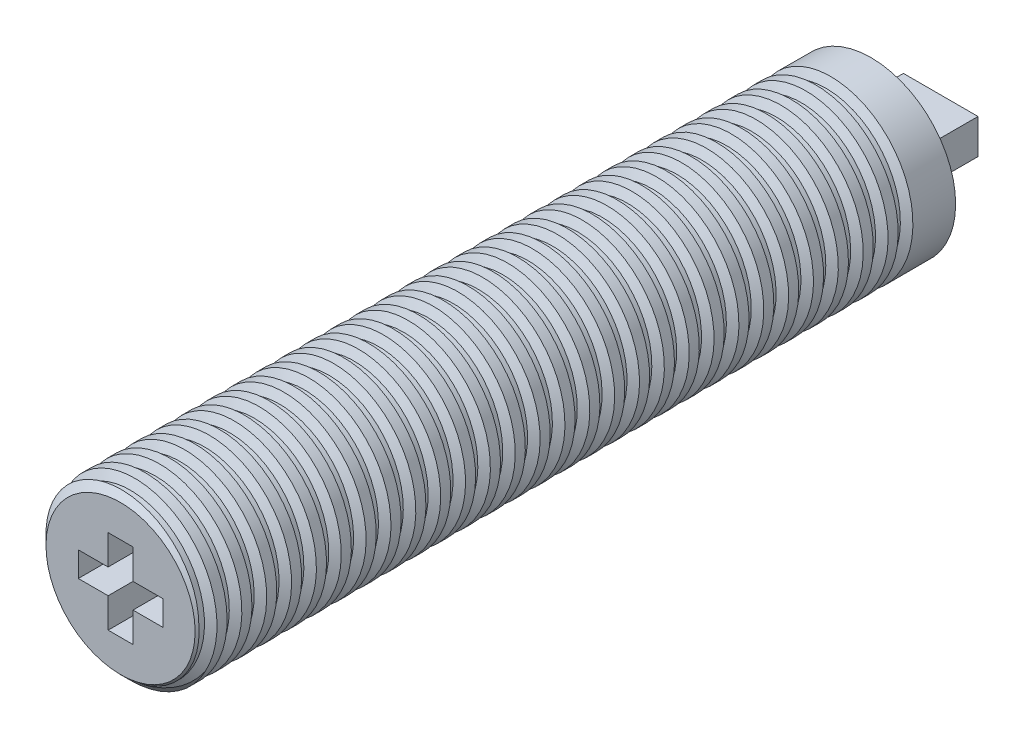
SolidWorks part; units mm, degrees
ref_plane "Front Plane" through (0, 0, 0) normal (0, 0, 1) x (1, 0, 0)
ref_plane "Top Plane" through (0, 0, 0) normal (0, 1, 0) x (1, 0, 0)
ref_plane "Right Plane" through (0, 0, 0) normal (1, 0, 0) x (0, 0, -1)
sketch "Sketch1" plane through (0, 0, 0) normal (0, 0, 1) x (1, 0, 0)
  circle A0 centre (0, 0) radius 8.5
  dimension "D1" = 17
extrude "Boss-Extrude1" add sketch "Sketch1" along normal blind 75.5
chamfer "Chamfer1" distance 1 angle 45 1 edges at (8.5, 0, 75.5)
ref_plane "Plane1" through (0, 0, 75.5) normal (0, 0, 1) x (1, 0, 0)
sketch "Sketch3" plane through (0, 0, 75.5) normal (0, 0, 1) x (1, 0, 0)
  circle A0 centre (0, 0) radius 8.5
  dimension "D1" = 17
sketch "Sketch4" plane through (0, 0, 0) normal (0, 1, 0) x (1, 0, 0)
  line L0 (-8.6, -75.5) -> (-8.6, -77.1)
  line L1 (-8.6, -77.1) -> (-7.7, -76.5804)
  line L2 (-7.7, -76.5804) -> (-7.7, -76.0196)
  line L3 (-7.7, -76.0196) -> (-8.6, -75.5)
  line L4 (-8.5, -74.5) -> (-8.5, -86.7444) construction
  dimension "D1" = 1.6
  dimension "D2" = 0.9
  dimension "D3" = 60
curve "Helix/Spiral1" pitch 2.5 height 72.5 radius 8.5 left hand yes centre (0, 0, 75.5) axis (0, 0, -1) start towards (1, 0, 0)
sweep "Cut-Sweep2" cut profiles "Sketch4" path "Helix/Spiral1"
sketch "Sketch6" plane through (0, 0, 0) normal (0, 0, 1) x (1, 0, 0)
  line L1 (3.75, 1.75) -> (-3.75, 1.75)
  line L2 (3.75, 1.75) -> (3.75, -1.75)
  line L3 (3.75, -1.75) -> (-3.75, -1.75)
  line L4 (-3.75, 1.75) -> (-3.75, -1.75)
  point P4 (0, 1.75)
  point P5 (-3.75, 0)
  dimension "D1" = 7.5
  dimension "D2" = 3.5
extrude "Boss-Extrude2" add sketch "Sketch6" against normal blind 7
sketch "Sketch7" plane through (0, 0, 0) normal (0, 0, 1) x (1, 0, 0)
  text T0 "<b>CCW</b>" font "Century Gothic" height 2.5
extrude "Cut-Extrude1" cut sketch "Sketch7" along normal blind 1.5
sketch "Sketch8" plane through (0, 0, 75.5) normal (0, 0, 1) x (1, 0, 0)
  line L1 (-4.25, 1.25) -> (4.25, 1.25)
  line L2 (-4.25, 1.25) -> (-4.25, -1.25)
  line L3 (-4.25, -1.25) -> (4.25, -1.25)
  line L4 (4.25, 1.25) -> (4.25, -1.25)
  line L5 (-1.25, 4.25) -> (1.25, 4.25)
  line L6 (-1.25, 4.25) -> (-1.25, -4.25)
  line L7 (-1.25, -4.25) -> (1.25, -4.25)
  line L8 (1.25, 4.25) -> (1.25, -4.25)
  point P8 (0, 4.25)
  point P9 (0, 1.25)
  point P10 (4.25, 0)
  point P11 (1.25, 0)
  point P12 (0, 0)
  dimension "D1" = 2.5
  dimension "D2" = 2.5
  dimension "D3" = 8.5
  dimension "D4" = 8.5
extrude "Cut-Extrude2" cut sketch "Sketch8" against normal blind 11 contours L8 L5 L6 L1 | L8 L1 L6 L3 | L1 L8 L3 L4 | L6 L1 L2 L3 | L8 L3 L6 L7 region at (-2.75, 0, 75.5) region at (0, 2.75, 75.5) region at (0, 0, 75.5) region at (2.75, 0, 75.5) region at (0, -2.75, 75.5)
